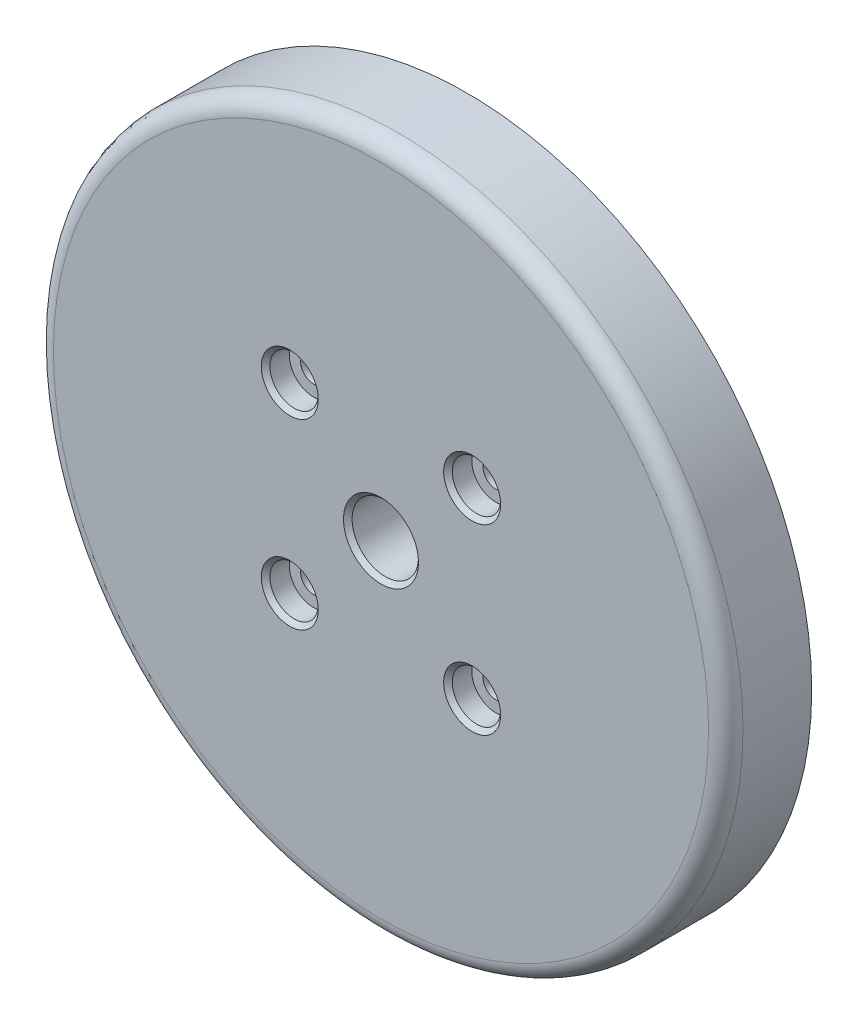
SolidWorks part; units mm, degrees
ref_plane "Front Plane" through (0, 0, 0) normal (0, 0, 1) x (1, 0, 0)
ref_plane "Top Plane" through (0, 0, 0) normal (0, 1, 0) x (1, 0, 0)
ref_plane "Right Plane" through (0, 0, 0) normal (1, 0, 0) x (0, 0, -1)
sketch "Sketch1" plane through (0, 0, 0) normal (0, 0, 1) x (1, 0, 0)
  circle A0 centre (0, 0) radius 50.927
  dimension "D1" = 101.854
extrude "Boss-Extrude1" add sketch "Sketch1" along normal blind 12.7
hole_wizard "W (0.386) Diameter Hole1" positions "Sketch2" profile "Sketch3" hole size "W" standard "ANSI Inch" end condition through all
sketch "Sketch2" plane through (0, 0, 12.7) normal (0, 0, 1) x (1, 0, 0)
  point P0 (0, 0)
sketch "Sketch3" plane through (0, 0, 12.7) normal (1, 0, 0) x (0, -1, 0)
  line L0 (0, 0) -> (0, 12.7)
  line L1 (0, 12.7) -> (4.9022, 12.7)
  line L2 (4.9022, 12.7) -> (4.9022, 0.635)
  line L3 (4.9022, 0.635) -> (5.5372, 0)
  line L5 (5.5372, 0) -> (0, 0)
  line L6 (-4.9022, 0.635) -> (-5.5372, 0) construction
  line L11 (0, -6.35) -> (0, 107.95) construction
  dimension "Thru Hole Dia." = 9.8044
  dimension "Thru Hole Depth" = 12.7
  dimension "Near C'Sink Dia." = 11.0744
  dimension "Near C'Sink Angle" = 90
hole_wizard "CBORE for #6 Socket Head Cap Screw1" positions "Sketch4" profile "Sketch5" counterbore size "#6" standard "ANSI Inch" end condition through all
sketch "Sketch4" plane through (0, 0, 12.7) normal (0, 0, 1) x (1, 0, 0)
  line L1 (-13.4704, -13.4704) -> (13.4704, -13.4704) construction
  line L2 (-13.4704, -13.4704) -> (-13.4704, 13.4704) construction
  line L3 (-13.4704, 13.4704) -> (13.4704, 13.4704) construction
  line L4 (13.4704, -13.4704) -> (13.4704, 13.4704) construction
  line L5 (-13.4704, -13.4704) -> (13.4704, 13.4704) construction
  line L6 (-13.4704, 13.4704) -> (13.4704, -13.4704) construction
  circle A1 centre (0, 0) radius 5.5372 construction
  point P2 (13.4704, 13.4704)
  point P87 (-13.4704, -13.4704)
  point P88 (-13.4704, 13.4704)
  point P89 (13.4704, -13.4704)
  dimension "D2" = 13.4704
  dimension "D1" = 38.1
  dimension "D3" = 13.4704
sketch "Sketch5" plane through (13.4704, 13.4704, 12.7) normal (1, 0, 0) x (0, -1, 0)
  line L0 (0, 0) -> (0, 12.7)
  line L1 (0, 12.7) -> (1.8986, 12.7)
  line L3 (1.8986, 12.7) -> (1.8986, 3.5052)
  line L4 (3.5725, 3.5052) -> (1.8986, 3.5052)
  line L5 (3.5725, 3.5052) -> (3.5725, 0.635)
  line L6 (3.5725, 0.635) -> (4.2075, 0)
  line L7 (4.2075, 0) -> (0, 0)
  line L8 (-3.5725, 0.635) -> (-4.2075, 0) construction
  line L11 (0, -6.35) -> (0, 107.95) construction
  dimension "Thru Hole Dia." = 3.7973
  dimension "Thru Hole Depth" = 12.7
  dimension "C'Bore Dia." = 7.145
  dimension "C'Bore Depth" = 3.5052
  dimension "Near C'Sink Dia." = 8.415
  dimension "Near C'Sink Angle" = 90
fillet "Fillet1" radius 2.54 1 edges at (50.927, 0, 12.7)
sketch "Sketch7" plane through (0, 0, 0) normal (0, 0, -1) x (-1, 0, 0)
  circle A0 centre (0, 0) radius 12.446
  circle A1 centre (0, 0) radius 15.9385
  dimension "D1" = 24.892
  dimension "D2" = 31.877
extrude "Cut-Extrude2" cut sketch "Sketch7" against normal blind 6.35
sketch "Sketch6" plane through (0, 0, 0) normal (0, 0, -1) x (-1, 0, 0)
  circle A0 centre (0, 0) radius 38.1
  dimension "D1" = 76.2
extrude "Cut-Extrude1" cut sketch "Sketch6" against normal blind 4.826
